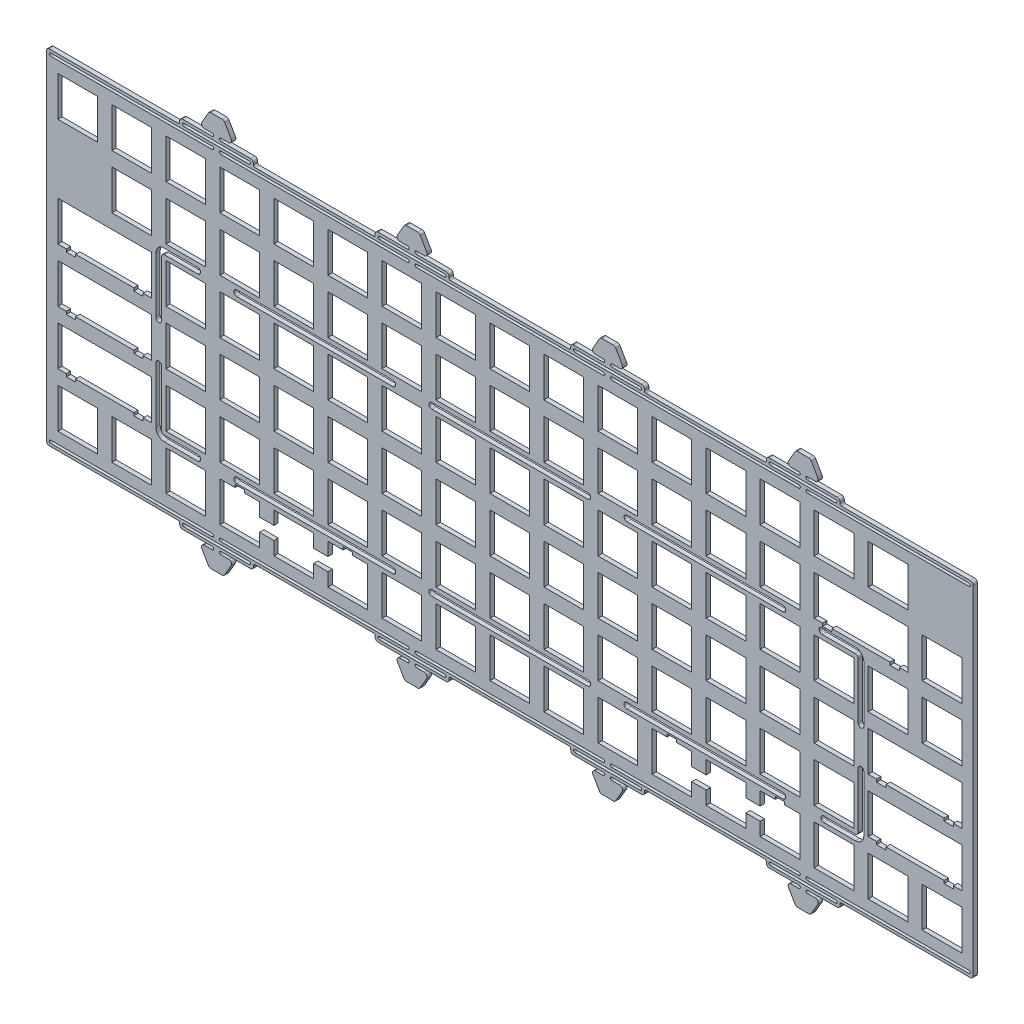
SolidWorks part; units mm, degrees
material "Acrylic (Medium-high impact)"
ref_plane "Front Plane" through (0, 0, 0) normal (0, 0, 1) x (1, 0, 0)
ref_plane "Top Plane" through (0, 0, 0) normal (0, 1, 0) x (1, 0, 0)
ref_plane "Right Plane" through (0, 0, 0) normal (1, 0, 0) x (0, 0, -1)
sketch "Sketch2" plane through (0, 0, 0) normal (0, 0, 1) x (1, 0, 0)
  line L0 (102.249, -54.6242) -> (102.249, -40.6233)
  line L1 (102.249, -40.6233) -> (96.9, -40.6233)
  line L2 (96.9, -40.6233) -> (96.9, -39.6546)
  line L3 (96.9, -39.6546) -> (93.6, -39.6546)
  line L4 (93.6, -39.6546) -> (93.6, -40.6233)
  line L5 (93.6, -40.6233) -> (88.25, -40.6233)
  line L6 (88.25, -40.6233) -> (88.25, -45.3238)
  line L7 (88.25, -45.3238) -> (83.199, -45.3238)
  line L8 (83.199, -45.3238) -> (83.199, -40.6233)
  line L9 (83.199, -40.6233) -> (69.2, -40.6233)
  line L10 (69.2, -40.6233) -> (69.2, -45.3238)
  line L11 (69.2, -45.3238) -> (64.149, -45.3238)
  line L12 (64.149, -45.3238) -> (64.149, -40.6233)
  line L13 (64.149, -40.6233) -> (58.801, -40.6233)
  line L14 (58.801, -40.6233) -> (58.801, -39.6546)
  line L15 (58.801, -39.6546) -> (55.5, -39.6546)
  line L16 (55.5, -39.6546) -> (55.5, -40.6233)
  line L17 (55.5, -40.6233) -> (50.15, -40.6233)
  line L18 (50.15, -40.6233) -> (50.15, -54.6242)
  line L19 (50.15, -54.6242) -> (64.149, -54.6242)
  line L20 (64.149, -54.6242) -> (64.149, -49.9223)
  line L21 (64.149, -49.9223) -> (69.2, -49.9223)
  line L22 (69.2, -49.9223) -> (69.2, -54.6242)
  line L23 (69.2, -54.6242) -> (83.199, -54.6242)
  line L24 (83.199, -54.6242) -> (83.199, -49.9223)
  line L25 (83.199, -49.9223) -> (88.25, -49.9223)
  line L26 (88.25, -49.9223) -> (88.25, -54.6242)
  line L27 (88.25, -54.6242) -> (102.249, -54.6242)
  line L28 (-50.1496, -54.6242) -> (-50.1496, -40.6233)
  line L29 (-50.1496, -40.6233) -> (-55.4991, -40.6233)
  line L30 (-55.4991, -40.6233) -> (-55.4991, -39.6546)
  line L31 (-55.4991, -39.6546) -> (-58.7994, -39.6546)
  line L32 (-58.7994, -39.6546) -> (-58.7994, -40.6233)
  line L33 (-58.7994, -40.6233) -> (-64.1503, -40.6233)
  line L34 (-64.1503, -40.6233) -> (-64.1503, -45.3238)
  line L35 (-64.1503, -45.3238) -> (-69.201, -45.3238)
  line L36 (-69.201, -45.3238) -> (-69.201, -40.6233)
  line L37 (-69.201, -40.6233) -> (-83.2003, -40.6233)
  line L38 (-83.2003, -40.6233) -> (-83.2003, -45.3238)
  line L39 (-83.2003, -45.3238) -> (-88.2496, -45.3238)
  line L40 (-88.2496, -45.3238) -> (-88.2496, -40.6233)
  line L41 (-88.2496, -40.6233) -> (-93.6003, -40.6233)
  line L42 (-93.6003, -40.6233) -> (-93.6003, -39.6546)
  line L43 (-93.6003, -39.6546) -> (-96.9003, -39.6546)
  line L44 (-96.9003, -39.6546) -> (-96.9003, -40.6233)
  line L45 (-96.9003, -40.6233) -> (-102.2503, -40.6233)
  line L46 (-102.2503, -40.6233) -> (-102.2503, -54.6242)
  line L47 (-102.2503, -54.6242) -> (-88.2496, -54.6242)
  line L48 (-88.2496, -54.6242) -> (-88.2496, -49.9223)
  line L49 (-88.2496, -49.9223) -> (-83.2003, -49.9223)
  line L50 (-83.2003, -49.9223) -> (-83.2003, -54.6242)
  line L51 (-83.2003, -54.6242) -> (-69.201, -54.6242)
  line L52 (-69.201, -54.6242) -> (-69.201, -49.9223)
  line L53 (-69.201, -49.9223) -> (-64.1503, -49.9223)
  line L54 (-64.1503, -49.9223) -> (-64.1503, -54.6242)
  line L55 (-64.1503, -54.6242) -> (-50.1496, -54.6242)
  line L56 (145.4, -40.6233) -> (159.399, -40.6233)
  line L57 (159.399, -40.6233) -> (159.399, -54.6242)
  line L58 (159.399, -54.6242) -> (145.4, -54.6242)
  line L59 (145.4, -54.6242) -> (145.4, -40.6233)
  line L60 (126.35, -40.6233) -> (140.349, -40.6233)
  line L61 (140.349, -40.6233) -> (140.349, -54.6242)
  line L62 (140.349, -54.6242) -> (126.35, -54.6242)
  line L63 (126.35, -54.6242) -> (126.35, -40.6233)
  line L64 (107.3, -40.6233) -> (121.299, -40.6233)
  line L65 (121.299, -40.6233) -> (121.299, -54.6242)
  line L66 (121.299, -54.6242) -> (107.3, -54.6242)
  line L67 (107.3, -54.6242) -> (107.3, -40.6233)
  line L68 (31.1, -40.6233) -> (45.099, -40.6233)
  line L69 (45.099, -40.6233) -> (45.099, -54.6242)
  line L70 (45.099, -54.6242) -> (31.1, -54.6242)
  line L71 (31.1, -54.6242) -> (31.1, -40.6233)
  line L72 (12.05, -40.6233) -> (26.049, -40.6233)
  line L73 (26.049, -40.6233) -> (26.049, -54.6242)
  line L74 (26.049, -54.6242) -> (12.05, -54.6242)
  line L75 (12.05, -54.6242) -> (12.05, -40.6233)
  line L76 (-7, -40.6233) -> (6.999, -40.6233)
  line L77 (6.999, -40.6233) -> (6.999, -54.6242)
  line L78 (6.999, -54.6242) -> (-7, -54.6242)
  line L79 (-7, -54.6242) -> (-7, -40.6233)
  line L80 (-26.05, -40.6233) -> (-12.051, -40.6233)
  line L81 (-12.051, -40.6233) -> (-12.051, -54.6242)
  line L82 (-12.051, -54.6242) -> (-26.05, -54.6242)
  line L83 (-26.05, -54.6242) -> (-26.05, -40.6233)
  line L84 (-45.102, -40.6233) -> (-31.101, -40.6233)
  line L85 (-31.101, -40.6233) -> (-31.101, -54.6242)
  line L86 (-31.101, -54.6242) -> (-45.102, -54.6242)
  line L87 (-45.102, -54.6242) -> (-45.102, -40.6233)
  line L88 (-121.3003, -40.6233) -> (-107.301, -40.6233)
  line L89 (-107.301, -40.6233) -> (-107.301, -54.6242)
  line L90 (-107.301, -54.6242) -> (-121.3003, -54.6242)
  line L91 (-121.3003, -54.6242) -> (-121.3003, -40.6233)
  line L92 (-140.3503, -40.6233) -> (-126.351, -40.6233)
  line L93 (-126.351, -40.6233) -> (-126.351, -54.6242)
  line L94 (-126.351, -54.6242) -> (-140.3503, -54.6242)
  line L95 (-140.3503, -54.6242) -> (-140.3503, -40.6233)
  line L96 (-159.4004, -40.6233) -> (-145.4008, -40.6233)
  line L97 (-145.4008, -40.6233) -> (-145.4008, -54.6242)
  line L98 (-145.4008, -54.6242) -> (-159.4004, -54.6242)
  line L99 (-159.4004, -54.6242) -> (-159.4004, -40.6233)
  line L100 (126.35, -21.5748) -> (126.35, -35.5742)
  line L101 (126.35, -35.5742) -> (129.325, -35.5742)
  line L102 (129.325, -35.5742) -> (129.325, -36.5443)
  line L103 (129.325, -36.5443) -> (132.624, -36.5443)
  line L104 (132.624, -36.5443) -> (132.624, -35.5742)
  line L105 (132.624, -35.5742) -> (153.125, -35.5742)
  line L106 (153.125, -35.5742) -> (153.125, -36.5443)
  line L107 (153.125, -36.5443) -> (156.424, -36.5443)
  line L108 (156.424, -36.5443) -> (156.424, -35.5742)
  line L109 (156.424, -35.5742) -> (159.399, -35.5742)
  line L110 (159.399, -35.5742) -> (159.399, -21.5748)
  line L111 (159.399, -21.5748) -> (126.35, -21.5748)
  line L112 (-159.4004, -21.5748) -> (-159.4004, -35.5742)
  line L113 (-159.4004, -35.5742) -> (-156.4252, -35.5742)
  line L114 (-156.4252, -35.5742) -> (-156.4252, -36.5443)
  line L115 (-156.4252, -36.5443) -> (-153.1262, -36.5443)
  line L116 (-153.1262, -36.5443) -> (-153.1262, -35.5742)
  line L117 (-153.1262, -35.5742) -> (-132.6251, -35.5742)
  line L118 (-132.6251, -35.5742) -> (-132.6251, -36.5443)
  line L119 (-132.6251, -36.5443) -> (-129.326, -36.5443)
  line L120 (-129.326, -36.5443) -> (-129.326, -35.5742)
  line L121 (-129.326, -35.5742) -> (-126.351, -35.5742)
  line L122 (-126.351, -35.5742) -> (-126.351, -21.5748)
  line L123 (-126.351, -21.5748) -> (-159.4004, -21.5748)
  line L124 (107.3, -21.5748) -> (121.299, -21.5748)
  line L125 (121.299, -21.5748) -> (121.299, -35.5742)
  line L126 (121.299, -35.5742) -> (107.3, -35.5742)
  line L127 (107.3, -35.5742) -> (107.3, -21.5748)
  line L128 (88.25, -21.5748) -> (102.249, -21.5748)
  line L129 (102.249, -21.5748) -> (102.249, -35.5742)
  line L130 (102.249, -35.5742) -> (88.25, -35.5742)
  line L131 (88.25, -35.5742) -> (88.25, -21.5748)
  line L132 (69.2, -21.5748) -> (83.199, -21.5748)
  line L133 (83.199, -21.5748) -> (83.199, -35.5742)
  line L134 (83.199, -35.5742) -> (69.2, -35.5742)
  line L135 (69.2, -35.5742) -> (69.2, -21.5748)
  line L136 (50.15, -21.5748) -> (64.149, -21.5748)
  line L137 (64.149, -21.5748) -> (64.149, -35.5742)
  line L138 (64.149, -35.5742) -> (50.15, -35.5742)
  line L139 (50.15, -35.5742) -> (50.15, -21.5748)
  line L140 (31.1, -21.5748) -> (45.099, -21.5748)
  line L141 (45.099, -21.5748) -> (45.099, -35.5742)
  line L142 (45.099, -35.5742) -> (31.1, -35.5742)
  line L143 (31.1, -35.5742) -> (31.1, -21.5748)
  line L144 (12.05, -21.5748) -> (26.049, -21.5748)
  line L145 (26.049, -21.5748) -> (26.049, -35.5742)
  line L146 (26.049, -35.5742) -> (12.05, -35.5742)
  line L147 (12.05, -35.5742) -> (12.05, -21.5748)
  line L148 (-7, -21.5748) -> (6.999, -21.5748)
  line L149 (6.999, -21.5748) -> (6.999, -35.5742)
  line L150 (6.999, -35.5742) -> (-7, -35.5742)
  line L151 (-7, -35.5742) -> (-7, -21.5748)
  line L152 (-26.05, -21.5748) -> (-12.051, -21.5748)
  line L153 (-12.051, -21.5748) -> (-12.051, -35.5742)
  line L154 (-12.051, -35.5742) -> (-26.05, -35.5742)
  line L155 (-26.05, -35.5742) -> (-26.05, -21.5748)
  line L156 (-45.102, -21.5748) -> (-31.101, -21.5748)
  line L157 (-31.101, -21.5748) -> (-31.101, -35.5742)
  line L158 (-31.101, -35.5742) -> (-45.102, -35.5742)
  line L159 (-45.102, -35.5742) -> (-45.102, -21.5748)
  line L160 (-64.1517, -21.5748) -> (-50.151, -21.5748)
  line L161 (-50.151, -21.5748) -> (-50.151, -35.5742)
  line L162 (-50.151, -35.5742) -> (-64.1517, -35.5742)
  line L163 (-64.1517, -35.5742) -> (-64.1517, -21.5748)
  line L164 (-83.2003, -21.5748) -> (-69.201, -21.5748)
  line L165 (-69.201, -21.5748) -> (-69.201, -35.5742)
  line L166 (-69.201, -35.5742) -> (-83.2003, -35.5742)
  line L167 (-83.2003, -35.5742) -> (-83.2003, -21.5748)
  line L168 (-102.2503, -21.5748) -> (-88.251, -21.5748)
  line L169 (-88.251, -21.5748) -> (-88.251, -35.5742)
  line L170 (-88.251, -35.5742) -> (-102.2503, -35.5742)
  line L171 (-102.2503, -35.5742) -> (-102.2503, -21.5748)
  line L172 (-121.3003, -21.5748) -> (-107.301, -21.5748)
  line L173 (-107.301, -21.5748) -> (-107.301, -35.5742)
  line L174 (-107.301, -35.5742) -> (-121.3003, -35.5742)
  line L175 (-121.3003, -35.5742) -> (-121.3003, -21.5748)
  line L176 (126.35, -2.5247) -> (126.35, -16.524)
  line L177 (126.35, -16.524) -> (129.325, -16.524)
  line L178 (129.325, -16.524) -> (129.325, -17.4942)
  line L179 (129.325, -17.4942) -> (132.624, -17.4942)
  line L180 (132.624, -17.4942) -> (132.624, -16.524)
  line L181 (132.624, -16.524) -> (153.125, -16.524)
  line L182 (153.125, -16.524) -> (153.125, -17.4942)
  line L183 (153.125, -17.4942) -> (156.424, -17.4942)
  line L184 (156.424, -17.4942) -> (156.424, -16.524)
  line L185 (156.424, -16.524) -> (159.399, -16.524)
  line L186 (159.399, -16.524) -> (159.399, -2.5247)
  line L187 (159.399, -2.5247) -> (126.35, -2.5247)
  line L188 (-159.4004, -2.5247) -> (-159.4004, -16.524)
  line L189 (-159.4004, -16.524) -> (-156.4252, -16.524)
  line L190 (-156.4252, -16.524) -> (-156.4252, -17.4942)
  line L191 (-156.4252, -17.4942) -> (-153.1262, -17.4942)
  line L192 (-153.1262, -17.4942) -> (-153.1262, -16.524)
  line L193 (-153.1262, -16.524) -> (-132.6251, -16.524)
  line L194 (-132.6251, -16.524) -> (-132.6251, -17.4942)
  line L195 (-132.6251, -17.4942) -> (-129.326, -17.4942)
  line L196 (-129.326, -17.4942) -> (-129.326, -16.524)
  line L197 (-129.326, -16.524) -> (-126.351, -16.524)
  line L198 (-126.351, -16.524) -> (-126.351, -2.5247)
  line L199 (-126.351, -2.5247) -> (-159.4004, -2.5247)
  line L200 (107.3, -2.5247) -> (121.299, -2.5247)
  line L201 (121.299, -2.5247) -> (121.299, -16.524)
  line L202 (121.299, -16.524) -> (107.3, -16.524)
  line L203 (107.3, -16.524) -> (107.3, -2.5247)
  line L204 (88.25, -2.5247) -> (102.249, -2.5247)
  line L205 (102.249, -2.5247) -> (102.249, -16.524)
  line L206 (102.249, -16.524) -> (88.25, -16.524)
  line L207 (88.25, -16.524) -> (88.25, -2.5247)
  line L208 (69.2, -2.5247) -> (83.199, -2.5247)
  line L209 (83.199, -2.5247) -> (83.199, -16.524)
  line L210 (83.199, -16.524) -> (69.2, -16.524)
  line L211 (69.2, -16.524) -> (69.2, -2.5247)
  line L212 (50.15, -2.5247) -> (64.149, -2.5247)
  line L213 (64.149, -2.5247) -> (64.149, -16.524)
  line L214 (64.149, -16.524) -> (50.15, -16.524)
  line L215 (50.15, -16.524) -> (50.15, -2.5247)
  line L216 (31.1, -2.5247) -> (45.099, -2.5247)
  line L217 (45.099, -2.5247) -> (45.099, -16.524)
  line L218 (45.099, -16.524) -> (31.1, -16.524)
  line L219 (31.1, -16.524) -> (31.1, -2.5247)
  line L220 (12.05, -2.5247) -> (26.049, -2.5247)
  line L221 (26.049, -2.5247) -> (26.049, -16.524)
  line L222 (26.049, -16.524) -> (12.05, -16.524)
  line L223 (12.05, -16.524) -> (12.05, -2.5247)
  line L224 (-7, -2.5247) -> (6.999, -2.5247)
  line L225 (6.999, -2.5247) -> (6.999, -16.524)
  line L226 (6.999, -16.524) -> (-7, -16.524)
  line L227 (-7, -16.524) -> (-7, -2.5247)
  line L228 (-26.05, -2.5247) -> (-12.051, -2.5247)
  line L229 (-12.051, -2.5247) -> (-12.051, -16.524)
  line L230 (-12.051, -16.524) -> (-26.05, -16.524)
  line L231 (-26.05, -16.524) -> (-26.05, -2.5247)
  line L232 (-45.102, -2.5247) -> (-31.101, -2.5247)
  line L233 (-31.101, -2.5247) -> (-31.101, -16.524)
  line L234 (-31.101, -16.524) -> (-45.102, -16.524)
  line L235 (-45.102, -16.524) -> (-45.102, -2.5247)
  line L236 (-64.1517, -2.5247) -> (-50.151, -2.5247)
  line L237 (-50.151, -2.5247) -> (-50.151, -16.524)
  line L238 (-50.151, -16.524) -> (-64.1517, -16.524)
  line L239 (-64.1517, -16.524) -> (-64.1517, -2.5247)
  line L240 (-83.2003, -2.5247) -> (-69.201, -2.5247)
  line L241 (-69.201, -2.5247) -> (-69.201, -16.524)
  line L242 (-69.201, -16.524) -> (-83.2003, -16.524)
  line L243 (-83.2003, -16.524) -> (-83.2003, -2.5247)
  line L244 (-102.2503, -2.5247) -> (-88.251, -2.5247)
  line L245 (-88.251, -2.5247) -> (-88.251, -16.524)
  line L246 (-88.251, -16.524) -> (-102.2503, -16.524)
  line L247 (-102.2503, -16.524) -> (-102.2503, -2.5247)
  line L248 (-121.3003, -2.5247) -> (-107.301, -2.5247)
  line L249 (-107.301, -2.5247) -> (-107.301, -16.524)
  line L250 (-107.301, -16.524) -> (-121.3003, -16.524)
  line L251 (-121.3003, -16.524) -> (-121.3003, -2.5247)
  line L252 (-159.4004, 16.5253) -> (-159.4004, 2.526)
  line L253 (-159.4004, 2.526) -> (-156.4252, 2.526)
  line L254 (-156.4252, 2.526) -> (-156.4252, 1.5558)
  line L255 (-156.4252, 1.5558) -> (-153.1262, 1.5558)
  line L256 (-153.1262, 1.5558) -> (-153.1262, 2.526)
  line L257 (-153.1262, 2.526) -> (-132.6251, 2.526)
  line L258 (-132.6251, 2.526) -> (-132.6251, 1.5558)
  line L259 (-132.6251, 1.5558) -> (-129.326, 1.5558)
  line L260 (-129.326, 1.5558) -> (-129.326, 2.526)
  line L261 (-129.326, 2.526) -> (-126.351, 2.526)
  line L262 (-126.351, 2.526) -> (-126.351, 16.5253)
  line L263 (-126.351, 16.5253) -> (-159.4004, 16.5253)
  line L264 (145.4, 16.5253) -> (159.399, 16.5253)
  line L265 (159.399, 16.5253) -> (159.399, 2.526)
  line L266 (159.399, 2.526) -> (145.4, 2.526)
  line L267 (145.4, 2.526) -> (145.4, 16.5253)
  line L268 (126.35, 16.5253) -> (140.349, 16.5253)
  line L269 (140.349, 16.5253) -> (140.349, 2.526)
  line L270 (140.349, 2.526) -> (126.35, 2.526)
  line L271 (126.35, 2.526) -> (126.35, 16.5253)
  line L272 (107.3, 16.5253) -> (121.299, 16.5253)
  line L273 (121.299, 16.5253) -> (121.299, 2.526)
  line L274 (121.299, 2.526) -> (107.3, 2.526)
  line L275 (107.3, 2.526) -> (107.3, 16.5253)
  line L276 (88.25, 16.5253) -> (102.249, 16.5253)
  line L277 (102.249, 16.5253) -> (102.249, 2.526)
  line L278 (102.249, 2.526) -> (88.25, 2.526)
  line L279 (88.25, 2.526) -> (88.25, 16.5253)
  line L280 (69.2, 16.5253) -> (83.199, 16.5253)
  line L281 (83.199, 16.5253) -> (83.199, 2.526)
  line L282 (83.199, 2.526) -> (69.2, 2.526)
  line L283 (69.2, 2.526) -> (69.2, 16.5253)
  line L284 (50.15, 16.5253) -> (64.149, 16.5253)
  line L285 (64.149, 16.5253) -> (64.149, 2.526)
  line L286 (64.149, 2.526) -> (50.15, 2.526)
  line L287 (50.15, 2.526) -> (50.15, 16.5253)
  line L288 (31.1, 16.5253) -> (45.099, 16.5253)
  line L289 (45.099, 16.5253) -> (45.099, 2.526)
  line L290 (45.099, 2.526) -> (31.1, 2.526)
  line L291 (31.1, 2.526) -> (31.1, 16.5253)
  line L292 (12.05, 16.5253) -> (26.049, 16.5253)
  line L293 (26.049, 16.5253) -> (26.049, 2.526)
  line L294 (26.049, 2.526) -> (12.05, 2.526)
  line L295 (12.05, 2.526) -> (12.05, 16.5253)
  line L296 (-7, 16.5253) -> (6.999, 16.5253)
  line L297 (6.999, 16.5253) -> (6.999, 2.526)
  line L298 (6.999, 2.526) -> (-7, 2.526)
  line L299 (-7, 2.526) -> (-7, 16.5253)
  line L300 (-26.05, 16.5253) -> (-12.051, 16.5253)
  line L301 (-12.051, 16.5253) -> (-12.051, 2.526)
  line L302 (-12.051, 2.526) -> (-26.05, 2.526)
  line L303 (-26.05, 2.526) -> (-26.05, 16.5253)
  line L304 (-45.102, 16.5253) -> (-31.101, 16.5253)
  line L305 (-31.101, 16.5253) -> (-31.101, 2.526)
  line L306 (-31.101, 2.526) -> (-45.102, 2.526)
  line L307 (-45.102, 2.526) -> (-45.102, 16.5253)
  line L308 (-64.1517, 16.5253) -> (-50.151, 16.5253)
  line L309 (-50.151, 16.5253) -> (-50.151, 2.526)
  line L310 (-50.151, 2.526) -> (-64.1517, 2.526)
  line L311 (-64.1517, 2.526) -> (-64.1517, 16.5253)
  line L312 (-83.2003, 16.5253) -> (-69.201, 16.5253)
  line L313 (-69.201, 16.5253) -> (-69.201, 2.526)
  line L314 (-69.201, 2.526) -> (-83.2003, 2.526)
  line L315 (-83.2003, 2.526) -> (-83.2003, 16.5253)
  line L316 (-102.2503, 16.5253) -> (-88.251, 16.5253)
  line L317 (-88.251, 16.5253) -> (-88.251, 2.526)
  line L318 (-88.251, 2.526) -> (-102.2503, 2.526)
  line L319 (-102.2503, 2.526) -> (-102.2503, 16.5253)
  line L320 (-121.3003, 16.5253) -> (-107.301, 16.5253)
  line L321 (-107.301, 16.5253) -> (-107.301, 2.526)
  line L322 (-107.301, 2.526) -> (-121.3003, 2.526)
  line L323 (-121.3003, 2.526) -> (-121.3003, 16.5253)
  line L324 (107.3, 35.5753) -> (107.3, 21.576)
  line L325 (107.3, 21.576) -> (110.275, 21.576)
  line L326 (110.275, 21.576) -> (110.275, 20.6058)
  line L327 (110.275, 20.6058) -> (113.574, 20.6058)
  line L328 (113.574, 20.6058) -> (113.574, 21.576)
  line L329 (113.574, 21.576) -> (134.075, 21.576)
  line L330 (134.075, 21.576) -> (134.075, 20.6058)
  line L331 (134.075, 20.6058) -> (137.374, 20.6058)
  line L332 (137.374, 20.6058) -> (137.374, 21.576)
  line L333 (137.374, 21.576) -> (140.349, 21.576)
  line L334 (140.349, 21.576) -> (140.349, 35.5753)
  line L335 (140.349, 35.5753) -> (107.3, 35.5753)
  line L336 (145.4, 35.5753) -> (159.399, 35.5753)
  line L337 (159.399, 35.5753) -> (159.399, 21.576)
  line L338 (159.399, 21.576) -> (145.4, 21.576)
  line L339 (145.4, 21.576) -> (145.4, 35.5753)
  line L340 (88.25, 35.5753) -> (102.249, 35.5753)
  line L341 (102.249, 35.5753) -> (102.249, 21.576)
  line L342 (102.249, 21.576) -> (88.25, 21.576)
  line L343 (88.25, 21.576) -> (88.25, 35.5753)
  line L344 (69.2, 35.5753) -> (83.199, 35.5753)
  line L345 (83.199, 35.5753) -> (83.199, 21.576)
  line L346 (83.199, 21.576) -> (69.2, 21.576)
  line L347 (69.2, 21.576) -> (69.2, 35.5753)
  line L348 (50.15, 35.5753) -> (64.149, 35.5753)
  line L349 (64.149, 35.5753) -> (64.149, 21.576)
  line L350 (64.149, 21.576) -> (50.15, 21.576)
  line L351 (50.15, 21.576) -> (50.15, 35.5753)
  line L352 (31.1, 35.5753) -> (45.099, 35.5753)
  line L353 (45.099, 35.5753) -> (45.099, 21.576)
  line L354 (45.099, 21.576) -> (31.1, 21.576)
  line L355 (31.1, 21.576) -> (31.1, 35.5753)
  line L356 (12.05, 35.5753) -> (26.049, 35.5753)
  line L357 (26.049, 35.5753) -> (26.049, 21.576)
  line L358 (26.049, 21.576) -> (12.05, 21.576)
  line L359 (12.05, 21.576) -> (12.05, 35.5753)
  line L360 (-7, 35.5753) -> (6.999, 35.5753)
  line L361 (6.999, 35.5753) -> (6.999, 21.576)
  line L362 (6.999, 21.576) -> (-7, 21.576)
  line L363 (-7, 21.576) -> (-7, 35.5753)
  line L364 (-26.05, 35.5753) -> (-12.051, 35.5753)
  line L365 (-12.051, 35.5753) -> (-12.051, 21.576)
  line L366 (-12.051, 21.576) -> (-26.05, 21.576)
  line L367 (-26.05, 21.576) -> (-26.05, 35.5753)
  line L368 (-45.102, 35.5753) -> (-31.101, 35.5753)
  line L369 (-31.101, 35.5753) -> (-31.101, 21.576)
  line L370 (-31.101, 21.576) -> (-45.102, 21.576)
  line L371 (-45.102, 21.576) -> (-45.102, 35.5753)
  line L372 (-64.1517, 35.5753) -> (-50.151, 35.5753)
  line L373 (-50.151, 35.5753) -> (-50.151, 21.576)
  line L374 (-50.151, 21.576) -> (-64.1517, 21.576)
  line L375 (-64.1517, 21.576) -> (-64.1517, 35.5753)
  line L376 (-83.2003, 35.5753) -> (-69.201, 35.5753)
  line L377 (-69.201, 35.5753) -> (-69.201, 21.576)
  line L378 (-69.201, 21.576) -> (-83.2003, 21.576)
  line L379 (-83.2003, 21.576) -> (-83.2003, 35.5753)
  line L380 (-102.2503, 35.5753) -> (-88.251, 35.5753)
  line L381 (-88.251, 35.5753) -> (-88.251, 21.576)
  line L382 (-88.251, 21.576) -> (-102.2503, 21.576)
  line L383 (-102.2503, 21.576) -> (-102.2503, 35.5753)
  line L384 (-121.3003, 35.5753) -> (-107.301, 35.5753)
  line L385 (-107.301, 35.5753) -> (-107.301, 21.576)
  line L386 (-107.301, 21.576) -> (-121.3003, 21.576)
  line L387 (-121.3003, 21.576) -> (-121.3003, 35.5753)
  line L388 (-140.3503, 35.5753) -> (-126.351, 35.5753)
  line L389 (-126.351, 35.5753) -> (-126.351, 21.576)
  line L390 (-126.351, 21.576) -> (-140.3503, 21.576)
  line L391 (-140.3503, 21.576) -> (-140.3503, 35.5753)
  line L392 (126.35, 54.6252) -> (140.349, 54.6252)
  line L393 (140.349, 54.6252) -> (140.349, 40.626)
  line L394 (140.349, 40.626) -> (126.35, 40.626)
  line L395 (126.35, 40.626) -> (126.35, 54.6252)
  line L396 (107.3, 54.6252) -> (121.299, 54.6252)
  line L397 (121.299, 54.6252) -> (121.299, 40.626)
  line L398 (121.299, 40.626) -> (107.3, 40.626)
  line L399 (107.3, 40.626) -> (107.3, 54.6252)
  line L400 (88.25, 54.6252) -> (102.249, 54.6252)
  line L401 (102.249, 54.6252) -> (102.249, 40.626)
  line L402 (102.249, 40.626) -> (88.25, 40.626)
  line L403 (88.25, 40.626) -> (88.25, 54.6252)
  line L404 (69.2, 54.6252) -> (83.199, 54.6252)
  line L405 (83.199, 54.6252) -> (83.199, 40.626)
  line L406 (83.199, 40.626) -> (69.2, 40.626)
  line L407 (69.2, 40.626) -> (69.2, 54.6252)
  line L408 (50.15, 54.6252) -> (64.149, 54.6252)
  line L409 (64.149, 54.6252) -> (64.149, 40.626)
  line L410 (64.149, 40.626) -> (50.15, 40.626)
  line L411 (50.15, 40.626) -> (50.15, 54.6252)
  line L412 (31.1, 54.6252) -> (45.099, 54.6252)
  line L413 (45.099, 54.6252) -> (45.099, 40.626)
  line L414 (45.099, 40.626) -> (31.1, 40.626)
  line L415 (31.1, 40.626) -> (31.1, 54.6252)
  line L416 (12.05, 54.6252) -> (26.049, 54.6252)
  line L417 (26.049, 54.6252) -> (26.049, 40.626)
  line L418 (26.049, 40.626) -> (12.05, 40.626)
  line L419 (12.05, 40.626) -> (12.05, 54.6252)
  line L420 (-7, 54.6252) -> (6.999, 54.6252)
  line L421 (6.999, 54.6252) -> (6.999, 40.626)
  line L422 (6.999, 40.626) -> (-7, 40.626)
  line L423 (-7, 40.626) -> (-7, 54.6252)
  line L424 (-26.05, 54.6252) -> (-12.051, 54.6252)
  line L425 (-12.051, 54.6252) -> (-12.051, 40.626)
  line L426 (-12.051, 40.626) -> (-26.05, 40.626)
  line L427 (-26.05, 40.626) -> (-26.05, 54.6252)
  line L428 (-45.102, 54.6252) -> (-31.101, 54.6252)
  line L429 (-31.101, 54.6252) -> (-31.101, 40.626)
  line L430 (-31.101, 40.626) -> (-45.102, 40.626)
  line L431 (-45.102, 40.626) -> (-45.102, 54.6252)
  line L432 (-64.1517, 54.6252) -> (-50.151, 54.6252)
  line L433 (-50.151, 54.6252) -> (-50.151, 40.626)
  line L434 (-50.151, 40.626) -> (-64.1517, 40.626)
  line L435 (-64.1517, 40.626) -> (-64.1517, 54.6252)
  line L436 (-83.2003, 54.6252) -> (-69.201, 54.6252)
  line L437 (-69.201, 54.6252) -> (-69.201, 40.626)
  line L438 (-69.201, 40.626) -> (-83.2003, 40.626)
  line L439 (-83.2003, 40.626) -> (-83.2003, 54.6252)
  line L440 (-102.2503, 54.6252) -> (-88.251, 54.6252)
  line L441 (-88.251, 54.6252) -> (-88.251, 40.626)
  line L442 (-88.251, 40.626) -> (-102.2503, 40.626)
  line L443 (-102.2503, 40.626) -> (-102.2503, 54.6252)
  line L444 (-121.3003, 54.6252) -> (-107.301, 54.6252)
  line L445 (-107.301, 54.6252) -> (-107.301, 40.626)
  line L446 (-107.301, 40.626) -> (-121.3003, 40.626)
  line L447 (-121.3003, 40.626) -> (-121.3003, 54.6252)
  line L448 (-140.3503, 54.6252) -> (-126.351, 54.6252)
  line L449 (-126.351, 54.6252) -> (-126.351, 40.626)
  line L450 (-126.351, 40.626) -> (-140.3503, 40.626)
  line L451 (-140.3503, 40.626) -> (-140.3503, 54.6252)
  line L452 (-159.4004, 54.6252) -> (-145.4008, 54.6252)
  line L453 (-145.4008, 54.6252) -> (-145.4008, 40.626)
  line L454 (-145.4008, 40.626) -> (-159.4004, 40.626)
  line L455 (-159.4004, 40.626) -> (-159.4004, 54.6252)
  line L456 (-162.4006, -55.6246) -> (-162.4006, 55.6256) construction
  line L457 (-160.4006, 57.6256) -> (160.3992, 57.6256) construction
  line L458 (162.3992, 55.6256) -> (162.3992, -55.6246) construction
  line L459 (160.3992, -57.6246) -> (-160.4006, -57.6246) construction
  line L461 (-172.4004, 69.6252) -> (172.399, 69.6252)
  line L462 (-172.4004, 69.6252) -> (-172.4004, -69.6242)
  line L463 (-172.4004, -69.6242) -> (172.399, -69.6242)
  line L464 (172.399, 69.6252) -> (172.399, -69.6242)
  circle A0 centre (-152.4006, 47.6256) radius 2 construction
  circle A1 centre (-133.3508, 47.6256) radius 2 construction
  circle A2 centre (-114.3008, 47.6256) radius 2 construction
  circle A3 centre (-95.2508, 47.6256) radius 2 construction
  circle A4 centre (-76.2008, 47.6256) radius 2 construction
  circle A5 centre (-57.1508, 47.6256) radius 2 construction
  circle A6 centre (-38.1008, 47.6256) radius 2 construction
  circle A7 centre (-19.0508, 47.6256) radius 2 construction
  circle A8 centre (-0.0008, 47.6256) radius 2 construction
  circle A9 centre (19.0492, 47.6256) radius 2 construction
  circle A10 centre (38.0992, 47.6256) radius 2 construction
  circle A11 centre (57.1492, 47.6256) radius 2 construction
  circle A12 centre (76.1992, 47.6256) radius 2 construction
  circle A13 centre (95.2492, 47.6256) radius 2 construction
  circle A14 centre (114.2992, 47.6256) radius 2 construction
  circle A15 centre (133.3492, 47.6256) radius 2 construction
  circle A16 centre (152.3992, 28.5756) radius 2 construction
  circle A17 centre (133.3492, 28.5756) radius 2 construction
  circle A18 centre (95.2492, 28.5756) radius 2 construction
  circle A19 centre (152.3992, 9.5256) radius 2 construction
  circle A20 centre (133.3492, 9.5256) radius 2 construction
  circle A21 centre (114.2992, 9.5256) radius 2 construction
  circle A22 centre (95.2492, 9.5256) radius 2 construction
  circle A23 centre (76.1992, 9.5256) radius 2 construction
  circle A24 centre (76.1992, 28.5756) radius 2 construction
  circle A25 centre (57.1492, 28.5756) radius 2 construction
  circle A26 centre (57.1492, 9.5256) radius 2 construction
  circle A27 centre (38.0992, 28.5756) radius 2 construction
  circle A28 centre (19.0492, 28.5756) radius 2 construction
  circle A29 centre (-0.0008, 28.5756) radius 2 construction
  circle A30 centre (-19.0508, 28.5756) radius 2 construction
  circle A31 centre (-38.1008, 28.5756) radius 2 construction
  circle A32 centre (-57.1508, 28.5756) radius 2 construction
  circle A33 centre (-76.2008, 28.5756) radius 2 construction
  circle A34 centre (-95.2508, 28.5756) radius 2 construction
  circle A35 centre (-114.3008, 28.5756) radius 2 construction
  circle A36 centre (-133.3508, 28.5756) radius 2 construction
  circle A37 centre (-133.3508, 9.5256) radius 2 construction
  circle A38 centre (-114.3008, 9.5256) radius 2 construction
  circle A39 centre (-133.3508, -9.5244) radius 2 construction
  circle A40 centre (-95.2508, 9.5256) radius 2 construction
  circle A41 centre (-76.2008, 9.5256) radius 2 construction
  circle A42 centre (-57.1508, 9.5256) radius 2 construction
  circle A43 centre (-38.1008, 9.5256) radius 2 construction
  circle A44 centre (-19.0508, 9.5256) radius 2 construction
  circle A45 centre (-0.0008, 9.5256) radius 2 construction
  circle A46 centre (19.0492, 9.5256) radius 2 construction
  circle A47 centre (38.0992, 9.5256) radius 2 construction
  circle A48 centre (152.3992, -9.5244) radius 2 construction
  circle A49 centre (152.3992, -28.5746) radius 2 construction
  circle A50 centre (152.3992, -47.6246) radius 2 construction
  circle A51 centre (133.3492, -47.6246) radius 2 construction
  circle A52 centre (114.2992, -47.6246) radius 2 construction
  circle A53 centre (95.2492, -47.6246) radius 2 construction
  circle A54 centre (114.2992, -28.5746) radius 2 construction
  circle A55 centre (95.2492, -28.5746) radius 2 construction
  circle A56 centre (76.1992, -47.6246) radius 2 construction
  circle A57 centre (57.1492, -47.6246) radius 2 construction
  circle A58 centre (57.1492, -28.5746) radius 2 construction
  circle A59 centre (57.1492, -9.5244) radius 2 construction
  circle A60 centre (76.1992, -9.5244) radius 2 construction
  circle A61 centre (76.1992, -28.5746) radius 2 construction
  circle A62 centre (95.2492, -9.5244) radius 2 construction
  circle A63 centre (114.2992, -9.5244) radius 2 construction
  circle A64 centre (38.0992, -9.5244) radius 2 construction
  circle A65 centre (38.0992, -28.5746) radius 2 construction
  circle A66 centre (38.0992, -47.6246) radius 2 construction
  circle A67 centre (19.0492, -28.5746) radius 2 construction
  circle A68 centre (19.0492, -9.5244) radius 2 construction
  circle A69 centre (19.0492, -47.6246) radius 2 construction
  circle A70 centre (-0.0008, -9.5244) radius 2 construction
  circle A71 centre (-19.0508, -9.5244) radius 2 construction
  circle A72 centre (-19.0508, -28.5746) radius 2 construction
  circle A73 centre (-0.0008, -28.5746) radius 2 construction
  circle A74 centre (-0.0008, -47.6246) radius 2 construction
  circle A75 centre (-19.0508, -47.6246) radius 2 construction
  circle A76 centre (-38.1008, -28.5746) radius 2 construction
  circle A77 centre (-38.1008, -9.5244) radius 2 construction
  circle A78 centre (-57.1508, -9.5244) radius 2 construction
  circle A79 centre (-38.1008, -47.6246) radius 2 construction
  circle A80 centre (-57.1494, -47.6246) radius 2 construction
  circle A81 centre (-57.1508, -28.5746) radius 2 construction
  circle A82 centre (-76.2008, -47.6246) radius 2 construction
  circle A83 centre (-76.2008, -28.5746) radius 2 construction
  circle A84 centre (-76.2008, -9.5244) radius 2 construction
  circle A85 centre (-95.2508, -9.5244) radius 2 construction
  circle A86 centre (-95.2508, -28.5746) radius 2 construction
  circle A87 centre (-95.2508, -47.6246) radius 2 construction
  circle A88 centre (-114.3008, -47.6246) radius 2 construction
  circle A89 centre (-114.3008, -28.5746) radius 2 construction
  circle A90 centre (-114.3008, -9.5244) radius 2 construction
  circle A91 centre (-133.3508, -28.5746) radius 2 construction
  circle A92 centre (-133.3508, -47.6246) radius 2 construction
  circle A93 centre (-152.4006, -47.6246) radius 2 construction
  circle A94 centre (-152.4006, 9.5256) radius 2 construction
  circle A95 centre (-152.4006, -9.5244) radius 2 construction
  circle A96 centre (-152.4006, -28.5746) radius 2 construction
  circle A97 centre (133.3497, -28.5746) radius 2 construction
  circle A98 centre (133.3497, -9.5244) radius 2 construction
  circle A99 centre (114.2997, 28.5756) radius 2 construction
  circle A100 centre (-142.8757, 9.5257) radius 2 construction
  circle A101 centre (-142.8757, -9.5243) radius 2 construction
  circle A102 centre (-142.8757, -28.5744) radius 2 construction
  circle A103 centre (142.8745, -28.5744) radius 2 construction
  circle A104 centre (142.8745, -9.5243) radius 2 construction
  circle A105 centre (123.8245, 28.5757) radius 2 construction
  arc A106 (-160.4006, 57.6256) -> (-162.4006, 55.6256) centre (-160.4006, 55.6256) ccw construction
  arc A107 (162.3992, 55.6256) -> (160.3992, 57.6256) centre (160.3992, 55.6256) ccw construction
  arc A108 (160.3992, -57.6246) -> (162.3992, -55.6246) centre (160.3992, -55.6246) ccw construction
  arc A109 (-162.4006, -55.6246) -> (-160.4006, -57.6246) centre (-160.4006, -55.6246) ccw construction
  point P680 (0, 0)
  dimension "D1" = 4
  dimension "D2" = 6.999
  dimension "D3" = 12.05
  dimension "D4" = 19.0492
  dimension "D5" = 26.049
  dimension "D6" = 31.1
  dimension "D7" = 38.0992
  dimension "D8" = 50.15
  dimension "D9" = 55.5
  dimension "D10" = 57.1492
  dimension "D11" = 58.801
  dimension "D12" = 69.2
  dimension "D13" = 76.1992
  dimension "D14" = 95.2492
  dimension "D15" = 96.9
  dimension "D16" = 107.3
  dimension "D17" = 110.275
  dimension "D18" = 113.574
  dimension "D19" = 114.2992
  dimension "D20" = 114.2997
  dimension "D21" = 123.8245
  dimension "D22" = 133.3492
  dimension "D23" = 133.3497
  dimension "D24" = 134.075
  dimension "D25" = 142.8745
  dimension "D26" = 152.3992
  dimension "D27" = 162.3992
  dimension "D28" = 0.0008
  dimension "D29" = 12.051
  dimension "D30" = 19.0508
  dimension "D31" = 31.101
  dimension "D32" = 38.1008
  dimension "D33" = 45.102
  dimension "D34" = 50.1496
  dimension "D35" = 50.151
  dimension "D36" = 55.4991
  dimension "D37" = 57.1494
  dimension "D38" = 57.1508
  dimension "D39" = 58.7994
  dimension "D40" = 64.1503
  dimension "D41" = 69.201
  dimension "D42" = 76.2008
  dimension "D43" = 83.2003
  dimension "D44" = 88.2496
  dimension "D45" = 95.2508
  dimension "D46" = 107.301
  dimension "D47" = 114.3008
  dimension "D48" = 126.351
  dimension "D49" = 132.6251
  dimension "D50" = 133.3508
  dimension "D51" = 142.8757
  dimension "D52" = 145.4008
  dimension "D53" = 152.4006
  dimension "D54" = 153.1262
  dimension "D55" = 159.4004
  dimension "D56" = 162.4006
  dimension "D57" = 1.5558
  dimension "D58" = 2.526
  dimension "D59" = 9.5256
  dimension "D60" = 9.5257
  dimension "D61" = 20.6058
  dimension "D62" = 28.5756
  dimension "D63" = 28.5757
  dimension "D64" = 40.626
  dimension "D65" = 47.6256
  dimension "D66" = 54.6252
  dimension "D67" = 57.6256
  dimension "D68" = 2.5247
  dimension "D69" = 9.5243
  dimension "D70" = 9.5244
  dimension "D71" = 21.5748
  dimension "D72" = 28.5744
  dimension "D73" = 28.5746
  dimension "D74" = 35.5742
  dimension "D75" = 39.6546
  dimension "D76" = 40.6233
  dimension "D77" = 45.3238
  dimension "D78" = 47.6246
  dimension "D79" = 49.9223
  dimension "D80" = 54.6242
  dimension "D81" = 57.6246
  dimension "D82" = 0.9701
  dimension "D83" = 172.399
  dimension "D84" = 69.6242
  dimension "D86" = 172.4004
  dimension "D87" = 69.6252
extrude "Boss-Extrude1" add sketch "Sketch2" along normal blind 1.524
sketch "Sketch3" plane through (0, 0, 1.524) normal (0, 0, 1) x (1, 0, 0)
  line L0 (-172.4004, -69.6242) -> (172.399, -69.6242) construction
  line L1 (-172.4004, -69.6242) -> (-103.4405, -69.6242) construction
  line L2 (-114.9405, -61.6242) -> (-91.9405, -61.6242)
  line L3 (-34.4807, -69.6242) -> (34.4792, -69.6242) construction
  line L4 (34.4792, -69.6242) -> (103.4391, -69.6242) construction
  line L5 (103.4391, -69.6242) -> (172.399, -69.6242) construction
  line L6 (-103.4405, -69.6242) -> (-103.4405, 85.065) construction
  line L7 (-34.4807, -69.6242) -> (-34.4807, 85.065) construction
  line L8 (34.4792, -69.6242) -> (34.4792, 85.065) construction
  line L9 (103.4391, -69.6242) -> (103.4391, 85.065) construction
  line L10 (-114.9405, -60.6242) -> (-91.9405, -60.6242)
  line L11 (-106.3065, -69.1242) -> (-108.6159, -65.1242)
  line L12 (-107.7499, -63.6242) -> (-104.9405, -63.6242)
  line L13 (-104.9405, -62.6242) -> (-115.4405, -62.6242)
  line L14 (-116.4405, -61.6242) -> (-116.4405, -61.1242)
  line L15 (-116.9405, -60.6242) -> (-137.9205, -60.6242)
  line L16 (-103.4405, -69.6242) -> (-34.4807, -69.6242) construction
  line L17 (-103.4405, -55.7341) -> (-172.4004, -55.7341) construction
  line L18 (-172.4004, 69.6252) -> (-172.4004, -69.6242) construction
  line L19 (-137.9205, -55.7341) -> (-137.9205, -69.6242) construction
  line L20 (-116.4405, -60.6242) -> (-137.9205, -60.6242) construction
  line L21 (-34.4807, -56.8321) -> (34.4792, -56.8321) construction
  line L25 (-103.4405, -60.6242) -> (-103.4405, -61.6242) construction
  line L26 (-105.4405, -69.6242) -> (-101.4405, -69.6242)
  line L27 (-100.5745, -69.1242) -> (-98.2651, -65.1242)
  line L28 (-99.1311, -63.6242) -> (-101.9405, -63.6242)
  line L29 (-101.9405, -62.6242) -> (-91.4405, -62.6242)
  line L30 (-90.4405, -61.6242) -> (-90.4405, -61.1242)
  line L31 (-89.9405, -60.6242) -> (-68.9606, -60.6242)
  line L32 (-47.9806, -60.6242) -> (-68.9606, -60.6242)
  line L33 (-47.4807, -61.6242) -> (-47.4807, -61.1242)
  line L34 (-35.9807, -62.6242) -> (-46.4807, -62.6242)
  line L35 (-45.9807, -61.6242) -> (-22.9807, -61.6242)
  line L36 (-38.7901, -63.6242) -> (-35.9807, -63.6242)
  line L37 (-37.3467, -69.1242) -> (-39.6561, -65.1242)
  line L38 (-36.4807, -69.6242) -> (-32.4807, -69.6242)
  line L39 (-31.6146, -69.1242) -> (-29.3052, -65.1242)
  line L40 (-30.1713, -63.6242) -> (-32.9807, -63.6242)
  line L41 (-32.9807, -62.6242) -> (-22.4807, -62.6242)
  line L42 (-21.4807, -61.6242) -> (-21.4807, -61.1242)
  line L43 (-20.9807, -60.6242) -> (-0.0007, -60.6242)
  line L44 (20.9792, -60.6242) -> (-0.0007, -60.6242)
  line L45 (21.4792, -61.6242) -> (21.4792, -61.1242)
  line L46 (32.9792, -62.6242) -> (22.4792, -62.6242)
  line L47 (22.9792, -61.6242) -> (45.9792, -61.6242)
  line L48 (30.1698, -63.6242) -> (32.9792, -63.6242)
  line L49 (31.6132, -69.1242) -> (29.3038, -65.1242)
  line L50 (32.4792, -69.6242) -> (36.4792, -69.6242)
  line L51 (37.3452, -69.1242) -> (39.6546, -65.1242)
  line L52 (38.7886, -63.6242) -> (35.9792, -63.6242)
  line L53 (35.9792, -62.6242) -> (46.4792, -62.6242)
  line L54 (47.4792, -61.6242) -> (47.4792, -61.1242)
  line L55 (47.9792, -60.6242) -> (68.9592, -60.6242)
  line L56 (89.9391, -60.6242) -> (68.9592, -60.6242)
  line L57 (90.4391, -61.6242) -> (90.4391, -61.1242)
  line L58 (101.9391, -62.6242) -> (91.4391, -62.6242)
  line L59 (91.9391, -61.6242) -> (114.9391, -61.6242)
  line L60 (99.1297, -63.6242) -> (101.9391, -63.6242)
  line L61 (100.5731, -69.1242) -> (98.2637, -65.1242)
  line L62 (101.4391, -69.6242) -> (105.4391, -69.6242)
  line L63 (106.3051, -69.1242) -> (108.6145, -65.1242)
  line L64 (107.7485, -63.6242) -> (104.9391, -63.6242)
  line L65 (104.9391, -62.6242) -> (115.4391, -62.6242)
  line L66 (116.4391, -61.6242) -> (116.4391, -61.1242)
  line L67 (116.9391, -60.6242) -> (137.919, -60.6242)
  line L68 (0, 0) -> (-214.8315, 0) construction
  line L69 (-45.9807, -60.6242) -> (-22.9807, -60.6242)
  line L70 (22.9792, -60.6242) -> (45.9792, -60.6242)
  line L71 (91.9391, -60.6242) -> (114.9391, -60.6242)
  line L72 (-137.9205, -60.6242) -> (-162.4004, -60.6242)
  line L73 (-0.0007, -69.6242) -> (-0.0007, 88.9307) construction
  line L74 (-152.7669, -60.6242) -> (-152.7669, -69.6242) construction
  line L75 (-163.4004, -47.018) -> (-172.4004, -47.018) construction
  line L76 (163.399, -59.6242) -> (163.399, 59.6242)
  line L77 (137.919, -60.6242) -> (162.399, -60.6242)
  line L78 (-163.4004, 47.018) -> (-172.4004, 47.018) construction
  line L79 (-163.4004, -59.6242) -> (-163.4004, 59.6242)
  line L80 (-152.7669, 60.6242) -> (-152.7669, 69.6242) construction
  line L81 (-103.4405, 60.6242) -> (-103.4405, 61.6242) construction
  line L82 (-34.4807, 56.8321) -> (34.4792, 56.8321) construction
  line L83 (-116.4405, 60.6242) -> (-137.9205, 60.6242) construction
  line L84 (-137.9205, 55.7341) -> (-137.9205, 69.6242) construction
  line L85 (-103.4405, 55.7341) -> (-172.4004, 55.7341) construction
  line L86 (-103.4405, 69.6242) -> (-34.4807, 69.6242) construction
  line L87 (34.4792, 69.6242) -> (103.4391, 69.6242) construction
  line L88 (-34.4807, 69.6242) -> (34.4792, 69.6242) construction
  line L89 (-172.4004, 69.6242) -> (-103.4405, 69.6242) construction
  line L90 (137.919, 60.6242) -> (162.399, 60.6242)
  line L91 (-137.9205, 60.6242) -> (-162.4004, 60.6242)
  line L92 (91.9391, 60.6242) -> (114.9391, 60.6242)
  line L93 (22.9792, 60.6242) -> (45.9792, 60.6242)
  line L94 (-45.9807, 60.6242) -> (-22.9807, 60.6242)
  line L95 (116.9391, 60.6242) -> (137.919, 60.6242)
  line L96 (116.4391, 61.6242) -> (116.4391, 61.1242)
  line L97 (104.9391, 62.6242) -> (115.4391, 62.6242)
  line L98 (107.7485, 63.6242) -> (104.9391, 63.6242)
  line L99 (106.3051, 69.1242) -> (108.6145, 65.1242)
  line L100 (101.4391, 69.6242) -> (105.4391, 69.6242)
  line L101 (100.5731, 69.1242) -> (98.2637, 65.1242)
  line L102 (99.1297, 63.6242) -> (101.9391, 63.6242)
  line L103 (91.9391, 61.6242) -> (114.9391, 61.6242)
  line L104 (101.9391, 62.6242) -> (91.4391, 62.6242)
  line L105 (90.4391, 61.6242) -> (90.4391, 61.1242)
  line L106 (89.9391, 60.6242) -> (68.9592, 60.6242)
  line L107 (47.9792, 60.6242) -> (68.9592, 60.6242)
  line L108 (47.4792, 61.6242) -> (47.4792, 61.1242)
  line L109 (35.9792, 62.6242) -> (46.4792, 62.6242)
  line L110 (38.7886, 63.6242) -> (35.9792, 63.6242)
  line L111 (37.3452, 69.1242) -> (39.6546, 65.1242)
  line L112 (32.4792, 69.6242) -> (36.4792, 69.6242)
  line L113 (31.6132, 69.1242) -> (29.3038, 65.1242)
  line L114 (30.1698, 63.6242) -> (32.9792, 63.6242)
  line L115 (22.9792, 61.6242) -> (45.9792, 61.6242)
  line L116 (32.9792, 62.6242) -> (22.4792, 62.6242)
  line L117 (21.4792, 61.6242) -> (21.4792, 61.1242)
  line L118 (20.9792, 60.6242) -> (-0.0007, 60.6242)
  line L119 (-20.9807, 60.6242) -> (-0.0007, 60.6242)
  line L120 (-21.4807, 61.6242) -> (-21.4807, 61.1242)
  line L121 (-32.9807, 62.6242) -> (-22.4807, 62.6242)
  line L122 (-30.1713, 63.6242) -> (-32.9807, 63.6242)
  line L123 (-31.6146, 69.1242) -> (-29.3052, 65.1242)
  line L124 (-36.4807, 69.6242) -> (-32.4807, 69.6242)
  line L125 (-37.3467, 69.1242) -> (-39.6561, 65.1242)
  line L126 (-38.7901, 63.6242) -> (-35.9807, 63.6242)
  line L127 (-45.9807, 61.6242) -> (-22.9807, 61.6242)
  line L128 (-35.9807, 62.6242) -> (-46.4807, 62.6242)
  line L129 (-47.4807, 61.6242) -> (-47.4807, 61.1242)
  line L130 (-47.9806, 60.6242) -> (-68.9606, 60.6242)
  line L131 (-89.9405, 60.6242) -> (-68.9606, 60.6242)
  line L132 (-90.4405, 61.6242) -> (-90.4405, 61.1242)
  line L133 (-101.9405, 62.6242) -> (-91.4405, 62.6242)
  line L134 (-99.1311, 63.6242) -> (-101.9405, 63.6242)
  line L135 (-100.5745, 69.1242) -> (-98.2651, 65.1242)
  line L136 (-105.4405, 69.6242) -> (-101.4405, 69.6242)
  line L137 (-116.9405, 60.6242) -> (-137.9205, 60.6242)
  line L138 (-116.4405, 61.6242) -> (-116.4405, 61.1242)
  line L139 (-104.9405, 62.6242) -> (-115.4405, 62.6242)
  line L140 (-107.7499, 63.6242) -> (-104.9405, 63.6242)
  line L141 (-106.3065, 69.1242) -> (-108.6159, 65.1242)
  line L142 (-114.9405, 60.6242) -> (-91.9405, 60.6242)
  line L143 (-114.9405, 61.6242) -> (-91.9405, 61.6242)
  line L144 (-101.9405, -59.1242) -> (-35.9807, -59.1242) construction
  line L149 (-101.9405, -59.6242) -> (-35.9807, -59.6242)
  line L150 (-101.9405, -58.6242) -> (-35.9807, -58.6242)
  line L151 (-68.9606, -60.6242) -> (-68.9606, 83.749) construction
  line L152 (68.9592, -60.6242) -> (68.9592, 77.0116) construction
  line L153 (-32.9807, -58.6242) -> (32.9792, -58.6242)
  line L154 (-32.9807, -59.6242) -> (32.9792, -59.6242)
  line L155 (35.9792, -58.6242) -> (101.9391, -58.6242)
  line L156 (35.9792, -59.6242) -> (101.9391, -59.6242)
  line L157 (-161.9046, -59.1242) -> (-104.9405, -59.1242) construction
  line L158 (-161.9046, -59.6242) -> (-104.9405, -59.6242)
  line L159 (-161.9046, -58.6242) -> (-104.9405, -58.6242)
  line L160 (161.9031, -58.6242) -> (104.9391, -58.6242)
  line L161 (161.9031, -59.6242) -> (104.9391, -59.6242)
  line L162 (161.9031, 59.6242) -> (104.9391, 59.6242)
  line L163 (161.9031, 58.6242) -> (104.9391, 58.6242)
  line L164 (35.9792, 59.6242) -> (101.9391, 59.6242)
  line L165 (35.9792, 58.6242) -> (101.9391, 58.6242)
  line L166 (-32.9807, 59.6242) -> (32.9792, 59.6242)
  line L167 (-32.9807, 58.6242) -> (32.9792, 58.6242)
  line L168 (-101.9405, 58.6242) -> (-35.9807, 58.6242)
  line L169 (-101.9405, 59.6242) -> (-35.9807, 59.6242)
  line L170 (-161.9046, 58.6242) -> (-104.9405, 58.6242)
  line L171 (-161.9046, 59.6242) -> (-104.9405, 59.6242)
  line L172 (-121.3003, 21.576) -> (-107.301, 21.576) construction
  line L173 (-123.8257, 19.0506) -> (-110.0674, 19.0506) construction
  line L174 (-123.8257, 19.0506) -> (-123.8257, 4.7633) construction
  line L175 (-123.8257, -38.0988) -> (-110.0674, -38.0988) construction
  line L176 (123.8245, 19.0506) -> (123.8245, 4.7633) construction
  line L177 (121.299, 2.526) -> (121.299, 16.5253) construction
  line L178 (126.35, 16.5253) -> (126.35, 2.526) construction
  line L179 (-107.301, -40.6233) -> (-121.3003, -40.6233) construction
  line L180 (-121.3003, -35.5742) -> (-107.301, -35.5742) construction
  line L181 (-121.3003, 16.5253) -> (-121.3003, 2.526) construction
  line L182 (-126.351, 2.526) -> (-126.351, 16.5253) construction
  line L183 (-107.301, 16.5253) -> (-121.3003, 16.5253) construction
  line L184 (121.299, 2.526) -> (121.299, 16.5253) construction
  line L185 (126.35, 16.5253) -> (126.35, 2.526) construction
  line L186 (-107.301, -40.6233) -> (-121.3003, -40.6233) construction
  line L187 (-121.3003, -35.5742) -> (-107.301, -35.5742) construction
  line L188 (-121.3003, 16.5253) -> (-121.3003, 2.526) construction
  line L189 (-126.351, 2.526) -> (-126.351, 16.5253) construction
  line L190 (-107.301, 16.5253) -> (-121.3003, 16.5253) construction
  line L191 (-121.3003, 21.576) -> (-107.301, 21.576) construction
  line L192 (123.8245, 4.7633) -> (123.8245, -9.5241) construction
  line L193 (123.8245, -9.5241) -> (123.8245, -23.8114) construction
  line L194 (123.8245, -23.8114) -> (123.8245, -38.0988) construction
  line L195 (-123.8257, 4.7633) -> (-123.8257, -9.5241) construction
  line L196 (-123.8257, -9.5241) -> (-123.8257, -23.8114) construction
  line L197 (-123.8257, -23.8114) -> (-123.8257, -38.0988) construction
  line L198 (-110.0674, 19.0506) -> (-96.309, 19.0506) construction
  line L199 (-96.309, 19.0506) -> (-82.5507, 19.0506) construction
  line L200 (-82.5507, 19.0506) -> (-68.7923, 19.0506) construction
  line L201 (-68.7923, 19.0506) -> (-55.034, 19.0506) construction
  line L202 (-55.034, 19.0506) -> (-41.2756, 19.0506) construction
  line L203 (-41.2756, 19.0506) -> (-27.5173, 19.0506) construction
  line L204 (-27.5173, 19.0506) -> (-13.759, 19.0506) construction
  line L205 (-13.759, 19.0506) -> (-0.0006, 19.0506) construction
  line L206 (-0.0006, 19.0506) -> (13.7577, 19.0506) construction
  line L207 (13.7577, 19.0506) -> (27.5161, 19.0506) construction
  line L208 (27.5161, 19.0506) -> (41.2744, 19.0506) construction
  line L209 (41.2744, 19.0506) -> (55.0327, 19.0506) construction
  line L210 (55.0327, 19.0506) -> (68.7911, 19.0506) construction
  line L211 (68.7911, 19.0506) -> (82.5494, 19.0506) construction
  line L212 (82.5494, 19.0506) -> (96.3078, 19.0506) construction
  line L213 (96.3078, 19.0506) -> (110.0661, 19.0506) construction
  line L214 (110.0661, 19.0506) -> (123.8245, 19.0506) construction
  line L215 (-123.8257, -36.0988) -> (-123.8257, -16.4041) construction
  line L216 (-27.5173, 19.0506) -> (27.5161, 19.0506) construction
  line L217 (-96.309, 19.0506) -> (-41.2756, 19.0506) construction
  line L218 (41.2744, 19.0506) -> (96.3078, 19.0506) construction
  line L219 (-110.0674, -38.0988) -> (-96.309, -38.0988) construction
  line L220 (-96.309, -38.0988) -> (-82.5507, -38.0988) construction
  line L221 (-82.5507, -38.0988) -> (-68.7923, -38.0988) construction
  line L222 (-68.7923, -38.0988) -> (-55.034, -38.0988) construction
  line L223 (-55.034, -38.0988) -> (-41.2756, -38.0988) construction
  line L224 (-41.2756, -38.0988) -> (-27.5173, -38.0988) construction
  line L225 (-27.5173, -38.0988) -> (-13.759, -38.0988) construction
  line L226 (-13.759, -38.0988) -> (-0.0006, -38.0988) construction
  line L227 (-0.0006, -38.0988) -> (13.7577, -38.0988) construction
  line L228 (13.7577, -38.0988) -> (27.5161, -38.0988) construction
  line L229 (27.5161, -38.0988) -> (41.2744, -38.0988) construction
  line L230 (41.2744, -38.0988) -> (55.0327, -38.0988) construction
  line L231 (55.0327, -38.0988) -> (68.7911, -38.0988) construction
  line L232 (68.7911, -38.0988) -> (82.5494, -38.0988) construction
  line L233 (82.5494, -38.0988) -> (96.3078, -38.0988) construction
  line L234 (96.3078, -38.0988) -> (110.0661, -38.0988) construction
  line L235 (110.0661, -38.0988) -> (123.8245, -38.0988) construction
  line L236 (-96.309, -38.0988) -> (-41.2756, -38.0988) construction
  line L237 (-27.5173, -38.0988) -> (27.5161, -38.0988) construction
  line L238 (41.2744, -38.0988) -> (96.3078, -38.0988) construction
  line L239 (-110.0674, 19.0506) -> (-121.8257, 19.0506) construction
  line L240 (-123.8257, 17.0506) -> (-123.8257, -2.6441) construction
  line L241 (-121.8257, -38.0988) -> (-110.0674, -38.0988) construction
  line L242 (110.7182, -38.0988) -> (121.8245, -38.0988) construction
  line L243 (123.8245, 17.0506) -> (123.8245, -2.6441) construction
  line L244 (123.8245, -36.0988) -> (123.8245, -16.4041) construction
  line L245 (121.8245, 19.0506) -> (110.0661, 19.0506) construction
  line L246 (-121.8257, -37.0988) -> (-110.0674, -37.0988)
  line L247 (-122.8257, -36.0988) -> (-122.8257, -16.4041)
  line L248 (-27.5173, 18.0506) -> (27.5161, 18.0506)
  line L249 (-96.309, 18.0506) -> (-41.2756, 18.0506)
  line L250 (41.2744, 18.0506) -> (96.3078, 18.0506)
  line L251 (-96.309, -39.0988) -> (-41.2756, -39.0988)
  line L252 (-27.5173, -39.0988) -> (27.5161, -39.0988)
  line L253 (41.2744, -39.0988) -> (96.3078, -39.0988)
  line L254 (-110.0674, 20.0506) -> (-121.8257, 20.0506)
  line L255 (-124.8257, 17.0506) -> (-124.8257, -2.6441)
  line L256 (110.7182, -39.0988) -> (121.8245, -39.0988)
  line L257 (124.8245, -36.0988) -> (124.8245, -16.4041)
  line L258 (121.8245, 18.0506) -> (110.0661, 18.0506)
  line L259 (122.8245, 17.0506) -> (122.8245, -2.6441)
  line L260 (-121.8257, -39.0988) -> (-110.0674, -39.0988)
  line L261 (-124.8257, -36.0988) -> (-124.8257, -16.4041)
  line L262 (-27.5173, 20.0506) -> (27.5161, 20.0506)
  line L263 (-96.309, 20.0506) -> (-41.2756, 20.0506)
  line L264 (41.2744, 20.0506) -> (96.3078, 20.0506)
  line L265 (-96.309, -37.0988) -> (-41.2756, -37.0988)
  line L266 (-27.5173, -37.0988) -> (27.5161, -37.0988)
  line L267 (41.2744, -37.0988) -> (96.3078, -37.0988)
  line L268 (-110.0674, 18.0506) -> (-121.8257, 18.0506)
  line L269 (-122.8257, 17.0506) -> (-122.8257, -2.6441)
  line L270 (110.7182, -37.0988) -> (121.8245, -37.0988)
  line L271 (122.8245, -36.0988) -> (122.8245, -16.4041)
  line L272 (121.8245, 20.0506) -> (110.0661, 20.0506)
  line L273 (124.8245, 17.0506) -> (124.8245, -2.6441)
  line L275 (-194.3659, 82.9947) -> (194.3659, 82.9947)
  line L276 (-194.3659, 82.9947) -> (-194.3659, -82.9947)
  line L277 (-194.3659, -82.9947) -> (194.3659, -82.9947)
  line L278 (194.3659, 82.9947) -> (194.3659, -82.9947)
  line L279 (-194.3659, 82.9947) -> (194.3659, -82.9947) construction
  line L280 (-194.3659, -82.9947) -> (194.3659, 82.9947) construction
  circle A0 centre (-103.4405, -66.6242) radius 2 construction
  arc A1 (-105.4405, -69.6242) -> (-106.3065, -69.1242) centre (-105.4405, -68.6242) cw
  arc A2 (-108.6159, -65.1242) -> (-107.7499, -63.6242) centre (-107.7499, -64.6242) cw
  arc A3 (-116.4405, -61.1242) -> (-116.9405, -60.6242) centre (-116.9405, -61.1242) ccw
  arc A6 (-104.9405, -62.6242) -> (-104.9405, -63.6242) centre (-104.9405, -63.1242) cw
  arc A7 (-114.9405, -60.6242) -> (-114.9405, -61.6242) centre (-114.9405, -61.1242) ccw
  arc A8 (-115.4405, -62.6242) -> (-116.4405, -61.6242) centre (-115.4405, -61.6242) cw
  arc A9 (-101.4405, -69.6242) -> (-100.5745, -69.1242) centre (-101.4405, -68.6242) ccw
  arc A10 (-98.2651, -65.1242) -> (-99.1311, -63.6242) centre (-99.1311, -64.6242) ccw
  arc A11 (-101.9405, -62.6242) -> (-101.9405, -63.6242) centre (-101.9405, -63.1242) ccw
  arc A12 (-91.9405, -60.6242) -> (-91.9405, -61.6242) centre (-91.9405, -61.1242) cw
  arc A13 (-91.4405, -62.6242) -> (-90.4405, -61.6242) centre (-91.4405, -61.6242) ccw
  arc A14 (-90.4405, -61.1242) -> (-89.9405, -60.6242) centre (-89.9405, -61.1242) cw
  arc A15 (-47.4807, -61.1242) -> (-47.9806, -60.6242) centre (-47.9806, -61.1242) ccw
  arc A16 (-46.4807, -62.6242) -> (-47.4807, -61.6242) centre (-46.4807, -61.6242) cw
  arc A17 (-22.9807, -60.6242) -> (-22.9807, -61.6242) centre (-22.9807, -61.1242) cw
  arc A18 (-45.9807, -60.6242) -> (-45.9807, -61.6242) centre (-45.9807, -61.1242) ccw
  arc A19 (-35.9807, -62.6242) -> (-35.9807, -63.6242) centre (-35.9807, -63.1242) cw
  arc A20 (-39.6561, -65.1242) -> (-38.7901, -63.6242) centre (-38.7901, -64.6242) cw
  arc A21 (-36.4807, -69.6242) -> (-37.3467, -69.1242) centre (-36.4807, -68.6242) cw
  arc A22 (-32.4807, -69.6242) -> (-31.6146, -69.1242) centre (-32.4807, -68.6242) ccw
  arc A23 (-29.3052, -65.1242) -> (-30.1713, -63.6242) centre (-30.1713, -64.6242) ccw
  arc A24 (-32.9807, -62.6242) -> (-32.9807, -63.6242) centre (-32.9807, -63.1242) ccw
  arc A25 (-22.4807, -62.6242) -> (-21.4807, -61.6242) centre (-22.4807, -61.6242) ccw
  arc A26 (-21.4807, -61.1242) -> (-20.9807, -60.6242) centre (-20.9807, -61.1242) cw
  circle A27 centre (-34.4807, -66.6242) radius 2 construction
  arc A28 (21.4792, -61.1242) -> (20.9792, -60.6242) centre (20.9792, -61.1242) ccw
  arc A29 (22.4792, -62.6242) -> (21.4792, -61.6242) centre (22.4792, -61.6242) cw
  arc A30 (45.9792, -60.6242) -> (45.9792, -61.6242) centre (45.9792, -61.1242) cw
  arc A31 (22.9792, -60.6242) -> (22.9792, -61.6242) centre (22.9792, -61.1242) ccw
  arc A32 (32.9792, -62.6242) -> (32.9792, -63.6242) centre (32.9792, -63.1242) cw
  arc A33 (29.3038, -65.1242) -> (30.1698, -63.6242) centre (30.1698, -64.6242) cw
  arc A34 (32.4792, -69.6242) -> (31.6132, -69.1242) centre (32.4792, -68.6242) cw
  arc A35 (36.4792, -69.6242) -> (37.3452, -69.1242) centre (36.4792, -68.6242) ccw
  arc A36 (39.6546, -65.1242) -> (38.7886, -63.6242) centre (38.7886, -64.6242) ccw
  arc A37 (35.9792, -62.6242) -> (35.9792, -63.6242) centre (35.9792, -63.1242) ccw
  arc A38 (46.4792, -62.6242) -> (47.4792, -61.6242) centre (46.4792, -61.6242) ccw
  arc A39 (47.4792, -61.1242) -> (47.9792, -60.6242) centre (47.9792, -61.1242) cw
  circle A40 centre (34.4792, -66.6242) radius 2 construction
  arc A41 (90.4391, -61.1242) -> (89.9391, -60.6242) centre (89.9391, -61.1242) ccw
  arc A42 (91.4391, -62.6242) -> (90.4391, -61.6242) centre (91.4391, -61.6242) cw
  arc A43 (114.9391, -60.6242) -> (114.9391, -61.6242) centre (114.9391, -61.1242) cw
  arc A44 (91.9391, -60.6242) -> (91.9391, -61.6242) centre (91.9391, -61.1242) ccw
  arc A45 (101.9391, -62.6242) -> (101.9391, -63.6242) centre (101.9391, -63.1242) cw
  arc A46 (98.2637, -65.1242) -> (99.1297, -63.6242) centre (99.1297, -64.6242) cw
  arc A47 (101.4391, -69.6242) -> (100.5731, -69.1242) centre (101.4391, -68.6242) cw
  arc A48 (105.4391, -69.6242) -> (106.3051, -69.1242) centre (105.4391, -68.6242) ccw
  arc A49 (108.6145, -65.1242) -> (107.7485, -63.6242) centre (107.7485, -64.6242) ccw
  arc A50 (104.9391, -62.6242) -> (104.9391, -63.6242) centre (104.9391, -63.1242) ccw
  arc A51 (115.4391, -62.6242) -> (116.4391, -61.6242) centre (115.4391, -61.6242) ccw
  arc A52 (116.4391, -61.1242) -> (116.9391, -60.6242) centre (116.9391, -61.1242) cw
  circle A53 centre (103.4391, -66.6242) radius 2 construction
  arc A54 (-162.4004, -60.6242) -> (-163.4004, -59.6242) centre (-162.4004, -59.6242) cw
  arc A55 (162.399, -60.6242) -> (163.399, -59.6242) centre (162.399, -59.6242) ccw
  circle A56 centre (103.4391, 66.6242) radius 2 construction
  circle A57 centre (34.4792, 66.6242) radius 2 construction
  circle A58 centre (-34.4807, 66.6242) radius 2 construction
  circle A59 centre (-103.4405, 66.6242) radius 2 construction
  arc A60 (162.399, 60.6242) -> (163.399, 59.6242) centre (162.399, 59.6242) cw
  arc A61 (-162.4004, 60.6242) -> (-163.4004, 59.6242) centre (-162.4004, 59.6242) ccw
  arc A62 (116.4391, 61.1242) -> (116.9391, 60.6242) centre (116.9391, 61.1242) ccw
  arc A63 (115.4391, 62.6242) -> (116.4391, 61.6242) centre (115.4391, 61.6242) cw
  arc A64 (104.9391, 62.6242) -> (104.9391, 63.6242) centre (104.9391, 63.1242) cw
  arc A65 (108.6145, 65.1242) -> (107.7485, 63.6242) centre (107.7485, 64.6242) cw
  arc A66 (105.4391, 69.6242) -> (106.3051, 69.1242) centre (105.4391, 68.6242) cw
  arc A67 (101.4391, 69.6242) -> (100.5731, 69.1242) centre (101.4391, 68.6242) ccw
  arc A68 (98.2637, 65.1242) -> (99.1297, 63.6242) centre (99.1297, 64.6242) ccw
  arc A69 (101.9391, 62.6242) -> (101.9391, 63.6242) centre (101.9391, 63.1242) ccw
  arc A70 (91.9391, 60.6242) -> (91.9391, 61.6242) centre (91.9391, 61.1242) cw
  arc A71 (114.9391, 60.6242) -> (114.9391, 61.6242) centre (114.9391, 61.1242) ccw
  arc A72 (91.4391, 62.6242) -> (90.4391, 61.6242) centre (91.4391, 61.6242) ccw
  arc A73 (90.4391, 61.1242) -> (89.9391, 60.6242) centre (89.9391, 61.1242) cw
  arc A74 (47.4792, 61.1242) -> (47.9792, 60.6242) centre (47.9792, 61.1242) ccw
  arc A75 (46.4792, 62.6242) -> (47.4792, 61.6242) centre (46.4792, 61.6242) cw
  arc A76 (35.9792, 62.6242) -> (35.9792, 63.6242) centre (35.9792, 63.1242) cw
  arc A77 (39.6546, 65.1242) -> (38.7886, 63.6242) centre (38.7886, 64.6242) cw
  arc A78 (36.4792, 69.6242) -> (37.3452, 69.1242) centre (36.4792, 68.6242) cw
  arc A79 (32.4792, 69.6242) -> (31.6132, 69.1242) centre (32.4792, 68.6242) ccw
  arc A80 (29.3038, 65.1242) -> (30.1698, 63.6242) centre (30.1698, 64.6242) ccw
  arc A81 (32.9792, 62.6242) -> (32.9792, 63.6242) centre (32.9792, 63.1242) ccw
  arc A82 (22.9792, 60.6242) -> (22.9792, 61.6242) centre (22.9792, 61.1242) cw
  arc A83 (45.9792, 60.6242) -> (45.9792, 61.6242) centre (45.9792, 61.1242) ccw
  arc A84 (22.4792, 62.6242) -> (21.4792, 61.6242) centre (22.4792, 61.6242) ccw
  arc A85 (21.4792, 61.1242) -> (20.9792, 60.6242) centre (20.9792, 61.1242) cw
  arc A86 (-21.4807, 61.1242) -> (-20.9807, 60.6242) centre (-20.9807, 61.1242) ccw
  arc A87 (-22.4807, 62.6242) -> (-21.4807, 61.6242) centre (-22.4807, 61.6242) cw
  arc A88 (-32.9807, 62.6242) -> (-32.9807, 63.6242) centre (-32.9807, 63.1242) cw
  arc A89 (-29.3052, 65.1242) -> (-30.1713, 63.6242) centre (-30.1713, 64.6242) cw
  arc A90 (-32.4807, 69.6242) -> (-31.6146, 69.1242) centre (-32.4807, 68.6242) cw
  arc A91 (-36.4807, 69.6242) -> (-37.3467, 69.1242) centre (-36.4807, 68.6242) ccw
  arc A92 (-39.6561, 65.1242) -> (-38.7901, 63.6242) centre (-38.7901, 64.6242) ccw
  arc A93 (-35.9807, 62.6242) -> (-35.9807, 63.6242) centre (-35.9807, 63.1242) ccw
  arc A94 (-45.9807, 60.6242) -> (-45.9807, 61.6242) centre (-45.9807, 61.1242) cw
  arc A95 (-22.9807, 60.6242) -> (-22.9807, 61.6242) centre (-22.9807, 61.1242) ccw
  arc A96 (-46.4807, 62.6242) -> (-47.4807, 61.6242) centre (-46.4807, 61.6242) ccw
  arc A97 (-47.4807, 61.1242) -> (-47.9806, 60.6242) centre (-47.9806, 61.1242) cw
  arc A98 (-90.4405, 61.1242) -> (-89.9405, 60.6242) centre (-89.9405, 61.1242) ccw
  arc A99 (-91.4405, 62.6242) -> (-90.4405, 61.6242) centre (-91.4405, 61.6242) cw
  arc A100 (-91.9405, 60.6242) -> (-91.9405, 61.6242) centre (-91.9405, 61.1242) ccw
  arc A101 (-101.9405, 62.6242) -> (-101.9405, 63.6242) centre (-101.9405, 63.1242) cw
  arc A102 (-98.2651, 65.1242) -> (-99.1311, 63.6242) centre (-99.1311, 64.6242) cw
  arc A103 (-101.4405, 69.6242) -> (-100.5745, 69.1242) centre (-101.4405, 68.6242) cw
  arc A104 (-115.4405, 62.6242) -> (-116.4405, 61.6242) centre (-115.4405, 61.6242) ccw
  arc A105 (-114.9405, 60.6242) -> (-114.9405, 61.6242) centre (-114.9405, 61.1242) cw
  arc A106 (-104.9405, 62.6242) -> (-104.9405, 63.6242) centre (-104.9405, 63.1242) ccw
  arc A107 (-116.4405, 61.1242) -> (-116.9405, 60.6242) centre (-116.9405, 61.1242) cw
  arc A108 (-108.6159, 65.1242) -> (-107.7499, 63.6242) centre (-107.7499, 64.6242) ccw
  arc A109 (-105.4405, 69.6242) -> (-106.3065, 69.1242) centre (-105.4405, 68.6242) ccw
  arc A110 (-101.9405, -59.6242) -> (-101.9405, -58.6242) centre (-101.9405, -59.1242) cw
  arc A111 (-35.9807, -59.6242) -> (-35.9807, -58.6242) centre (-35.9807, -59.1242) ccw
  arc A112 (-32.9807, -59.6242) -> (-32.9807, -58.6242) centre (-32.9807, -59.1242) cw
  arc A113 (32.9792, -59.6242) -> (32.9792, -58.6242) centre (32.9792, -59.1242) ccw
  arc A114 (35.9792, -59.6242) -> (35.9792, -58.6242) centre (35.9792, -59.1242) cw
  arc A115 (101.9391, -59.6242) -> (101.9391, -58.6242) centre (101.9391, -59.1242) ccw
  arc A116 (-161.9046, -59.6242) -> (-161.9046, -58.6242) centre (-161.9046, -59.1242) cw
  arc A117 (-104.9405, -59.6242) -> (-104.9405, -58.6242) centre (-104.9405, -59.1242) ccw
  arc A118 (161.9031, -59.6242) -> (161.9031, -58.6242) centre (161.9031, -59.1242) ccw
  arc A119 (104.9391, -59.6242) -> (104.9391, -58.6242) centre (104.9391, -59.1242) cw
  arc A120 (104.9391, 59.6242) -> (104.9391, 58.6242) centre (104.9391, 59.1242) ccw
  arc A121 (161.9031, 59.6242) -> (161.9031, 58.6242) centre (161.9031, 59.1242) cw
  arc A122 (35.9792, 59.6242) -> (35.9792, 58.6242) centre (35.9792, 59.1242) ccw
  arc A123 (101.9391, 59.6242) -> (101.9391, 58.6242) centre (101.9391, 59.1242) cw
  arc A124 (-32.9807, 59.6242) -> (-32.9807, 58.6242) centre (-32.9807, 59.1242) ccw
  arc A125 (32.9792, 59.6242) -> (32.9792, 58.6242) centre (32.9792, 59.1242) cw
  arc A126 (-101.9405, 59.6242) -> (-101.9405, 58.6242) centre (-101.9405, 59.1242) ccw
  arc A127 (-35.9807, 59.6242) -> (-35.9807, 58.6242) centre (-35.9807, 59.1242) cw
  arc A128 (-161.9046, 59.6242) -> (-161.9046, 58.6242) centre (-161.9046, 59.1242) ccw
  arc A129 (-104.9405, 59.6242) -> (-104.9405, 58.6242) centre (-104.9405, 59.1242) cw
  arc A130 (121.8245, 19.0506) -> (123.8245, 17.0506) centre (121.8245, 17.0506) cw construction
  arc A131 (121.8245, -38.0988) -> (123.8245, -36.0988) centre (121.8245, -36.0988) ccw construction
  arc A132 (-121.8257, -38.0988) -> (-123.8257, -36.0988) centre (-121.8257, -36.0988) cw construction
  arc A133 (-121.8257, 19.0506) -> (-123.8257, 17.0506) centre (-121.8257, 17.0506) ccw construction
  arc A134 (-121.8257, -37.0988) -> (-122.8257, -36.0988) centre (-121.8257, -36.0988) cw
  arc A135 (-121.8257, 20.0506) -> (-124.8257, 17.0506) centre (-121.8257, 17.0506) ccw
  arc A136 (121.8245, -39.0988) -> (124.8245, -36.0988) centre (121.8245, -36.0988) ccw
  arc A137 (121.8245, 18.0506) -> (122.8245, 17.0506) centre (121.8245, 17.0506) cw
  arc A138 (-121.8257, -39.0988) -> (-124.8257, -36.0988) centre (-121.8257, -36.0988) cw
  arc A139 (-121.8257, 18.0506) -> (-122.8257, 17.0506) centre (-121.8257, 17.0506) ccw
  arc A140 (121.8245, -37.0988) -> (122.8245, -36.0988) centre (121.8245, -36.0988) ccw
  arc A141 (121.8245, 20.0506) -> (124.8245, 17.0506) centre (121.8245, 17.0506) cw
  arc A142 (-110.0674, -37.0988) -> (-110.0674, -39.0988) centre (-110.0674, -38.0988) cw
  arc A143 (-122.8257, -16.4041) -> (-124.8257, -16.4041) centre (-123.8257, -16.4041) ccw
  arc A144 (-27.5173, 18.0506) -> (-27.5173, 20.0506) centre (-27.5173, 19.0506) cw
  arc A145 (27.5161, 18.0506) -> (27.5161, 20.0506) centre (27.5161, 19.0506) ccw
  arc A146 (-96.309, 18.0506) -> (-96.309, 20.0506) centre (-96.309, 19.0506) cw
  arc A147 (-41.2756, 18.0506) -> (-41.2756, 20.0506) centre (-41.2756, 19.0506) ccw
  arc A148 (41.2744, 18.0506) -> (41.2744, 20.0506) centre (41.2744, 19.0506) cw
  arc A149 (96.3078, 18.0506) -> (96.3078, 20.0506) centre (96.3078, 19.0506) ccw
  arc A150 (-96.309, -39.0988) -> (-96.309, -37.0988) centre (-96.309, -38.0988) cw
  arc A151 (-41.2756, -39.0988) -> (-41.2756, -37.0988) centre (-41.2756, -38.0988) ccw
  arc A152 (-27.5173, -39.0988) -> (-27.5173, -37.0988) centre (-27.5173, -38.0988) cw
  arc A153 (27.5161, -39.0988) -> (27.5161, -37.0988) centre (27.5161, -38.0988) ccw
  arc A154 (41.2744, -39.0988) -> (41.2744, -37.0988) centre (41.2744, -38.0988) cw
  arc A155 (96.3078, -39.0988) -> (96.3078, -37.0988) centre (96.3078, -38.0988) ccw
  arc A156 (-110.0674, 20.0506) -> (-110.0674, 18.0506) centre (-110.0674, 19.0506) cw
  arc A157 (-124.8257, -2.6441) -> (-122.8257, -2.6441) centre (-123.8257, -2.6441) ccw
  arc A158 (110.7182, -39.0988) -> (110.7182, -37.0988) centre (110.7182, -38.0988) cw
  arc A159 (124.8245, -16.4041) -> (122.8245, -16.4041) centre (123.8245, -16.4041) ccw
  arc A160 (110.0661, 18.0506) -> (110.0661, 20.0506) centre (110.0661, 19.0506) cw
  arc A161 (122.8245, -2.6441) -> (124.8245, -2.6441) centre (123.8245, -2.6441) ccw
  point P49 (-116.4405, -62.6242)
  point P379 (-163.4004, 0)
  point P380 (163.399, 0)
  point P383 (-116.4405, 62.6242)
  point P385 (-68.9606, -59.1242)
  point P466 (-123.8257, -9.5241)
  point P468 (68.7911, 19.0506)
  point P470 (-0.0006, 19.0506)
  point P472 (-68.7923, 19.0506)
  point P476 (68.7911, -38.0988)
  point P480 (-68.7923, -38.0988)
  point P484 (-0.0006, -38.0988)
  dimension "D1" = 4
  dimension "D12" = 1
  dimension "D13" = 0.5
  dimension "D14" = 1
  dimension "D8" = 1.5
  dimension "D15" = 1
  dimension "D16" = 12
  dimension "D7" = 1
  dimension "D19" = 0.5
  dimension "D20" = 0.5
  dimension "D21" = 3
  dimension "D18" = 1
  dimension "D29" = 2
  dimension "D2" = 2
  dimension "D3" = 1
  dimension "D4" = 1
  dimension "D5" = 1
  dimension "D6" = 1
  dimension "D9" = 1
  dimension "D10" = 2
  dimension "D11" = 120
  dimension "D17" = 4
  dimension "D22" = 0.5
  dimension "D24" = 57.1494
  dimension "D25" = 247.6501
  dimension "D26" = 19.0506
  dimension "D27" = 123.8257
  dimension "D28" = 13.76
  dimension "D23" = 0.5
  dimension "D30" = 1
  dimension "D31" = 1
extrude "Cut-Extrude1" cut sketch "Sketch3" against normal through all contours A109 L136 A103 L135 A102 L134 A101 L133 A99 L132 A98 L131 L130 A97 L129 A96 L128 A93 L126 A92 L125 A91 L124 A90 L123 A89 L122 A88 L121 A87 L120 A86 L119 L118 A85 L117 A84 L116 A81 L114 A80 L113 A79 L112 A78 L111 | L94 A95 L127 A94 | L92 A71 L103 A70 | L93 A83 L115 A82 | L71 A44 L59 A43 | L70 A31 L47 A30 | A12 L10 A7 L2 | L69 A18 L35 A17 | L247 A143 L261 A138 L260 A142 L246 A134 | L251 A151 L265 A150 | L154 A113 L153 A112 | L252 A153 L266 A152 | A119 L161 L76 L160 | L259 A161 L273 A141 L272 A160 L258 A137 | L162 A120 L163 L76 | L248 A145 L262 A144 | A127 L169 A126 L168 | L249 A147 L263 A146 | A129 L171 L79 L170 | L255 A157 L269 A139 L268 A156 L254 A135 | L171 A128 L170 L79 | L161 A118 L160 L76 | A121 L162 L76 L163 | L142 A100 L143 A105 | L158 A117 L159 A116 | L149 A111 L150 A110 | L253 A155 L267 A154 | L155 A115 L156 A114 | L270 A140 L271 A159 L257 A136 L256 A158 | L164 A123 L165 A122 | L250 A149 L264 A148 | L166 A125 L167 A124 region at (-103.4405, -61.1242, 1.524) region at (-34.4807, -61.1242, 1.524) region at (34.4792, -61.1242, 1.524) region at (103.4391, -61.1242, 1.524) region at (103.4391, 61.1242, 1.524) region at (34.4792, 61.1242, 1.524) region at (-34.4807, 61.1242, 1.524) region at (-0.0007, -59.1242, 1.524) region at (133.4211, -59.1242, 1.524) region at (133.4211, 59.1242, 1.524) region at (-68.9606, 59.1242, 1.524) region at (-133.4225, 59.1242, 1.524) region at (-115.9465, -37.3834, 1.524) region at (-0.0006, 19.0506, 1.524) region at (-68.7923, 19.0506, 1.524) region at (-68.7923, -38.0988, 1.524) region at (-0.0006, -38.0988, 1.524) region at (-109.3519, 19.0506, 1.524) region at (115.9453, 18.3352, 1.524) region at (0, 78.7678, 1.524)
